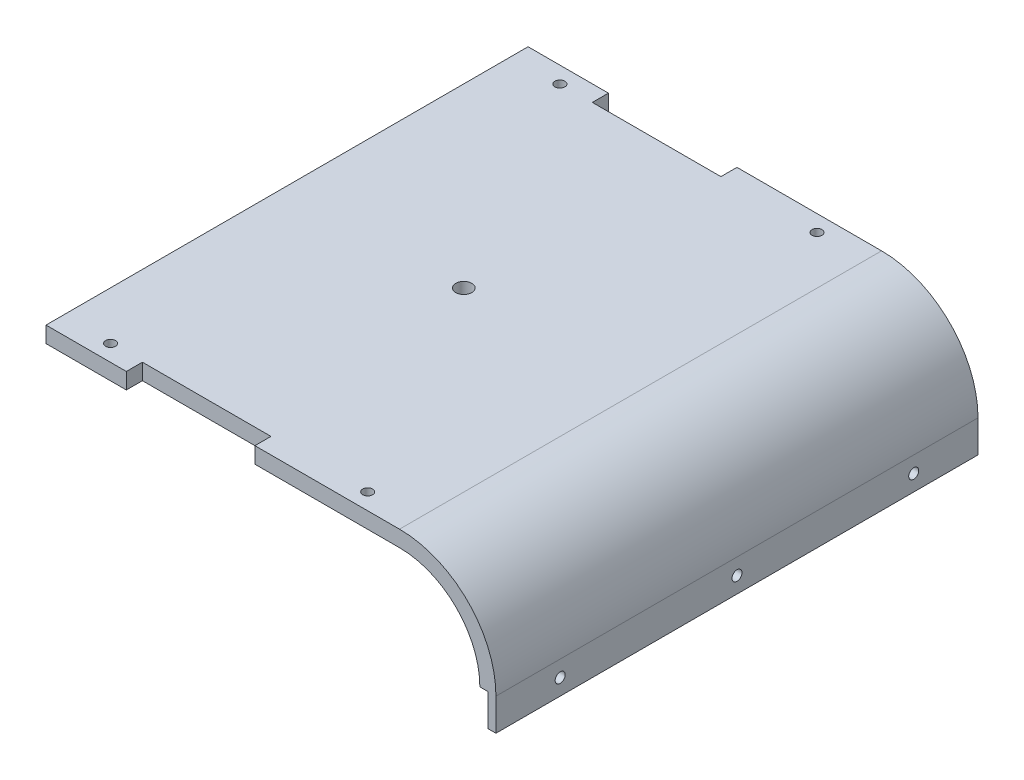
SolidWorks part; units mm, degrees
ref_plane "Front Plane" through (0, 0, 0) normal (0, 0, 1) x (1, 0, 0)
ref_plane "Top Plane" through (0, 0, 0) normal (0, 1, 0) x (1, 0, 0)
ref_plane "Right Plane" through (0, 0, 0) normal (1, 0, 0) x (0, 0, -1)
sketch "Sketch1" plane through (0, 0, 0) normal (0, 0, 1) x (1, 0, 0)
  line L0 (-139.7, 0) -> (139.7, 0)
  line L1 (139.7, 0) -> (139.7, -152.4) construction
  line L2 (139.7, -76.2) -> (215.9, -76.2) construction
  line L3 (-139.7, -12.7) -> (139.7, -12.7)
  line L4 (-139.7, 0) -> (-139.7, -12.7)
  line L5 (215.9, -76.2) -> (203.2, -76.2)
  circle A0 centre (139.7, -76.2) radius 76.2 construction
  arc A1 (139.7, 0) -> (215.9, -76.2) centre (139.7, -76.2) cw
  arc A2 (139.7, -12.7) -> (203.2, -76.2) centre (139.7, -76.2) cw
  point P4 (0, 0)
  dimension "D1" = 152.4
  dimension "D2" = 355.6
  dimension "D3" = 12.7
extrude "Boss-Extrude1" add sketch "Sketch1" along normal blind 190.5 and the other way blind 190.5
sketch "Sketch2" plane through (0, -76.2, 0) normal (0, -1, 0) x (1, 0, 0)
  line L0 (203.2, 190.5) -> (215.9, 190.5) construction
  line L1 (209.55, 190.5) -> (215.9, 190.5)
  line L2 (209.55, 190.5) -> (209.55, -190.5)
  line L3 (209.55, -190.5) -> (215.9, -190.5)
  line L4 (215.9, 190.5) -> (215.9, -190.5)
extrude "Boss-Extrude2" add sketch "Sketch2" along normal blind 25.4
sketch "Sketch3" plane through (215.9, 0, 0) normal (1, 0, 0) x (0, 0, -1)
  line L0 (-190.5, -88.9) -> (190.5, -88.9) construction
  line L1 (-190.5, -101.6) -> (-190.5, -76.2) construction
  line L2 (190.5, -101.6) -> (190.5, -76.2) construction
  line L3 (0, -76.2) -> (0, -101.6) construction
  line L4 (190.5, -76.2) -> (-190.5, -76.2) construction
  line L5 (190.5, -101.6) -> (-190.5, -101.6) construction
  line L6 (139.7, -76.2) -> (139.7, -101.6) construction
  line L7 (-139.7, -76.2) -> (-139.7, -101.6) construction
  circle A0 centre (-139.7, -88.9) radius 3.9687
  circle A1 centre (0, -88.9) radius 3.9687
  circle A2 centre (139.7, -88.9) radius 3.9687
  dimension "D3" = 7.9375
  dimension "D1" = 139.7
  dimension "D2" = 139.7
extrude "Cut-Extrude1" cut sketch "Sketch3" against normal blind 25.4
sketch "Sketch4" plane through (0, 0, 0) normal (0, 1, 0) x (1, 0, 0)
  circle A0 centre (0, 0) radius 6.35
  dimension "D1" = 12.7
extrude "Cut-Extrude2" cut sketch "Sketch4" against normal blind 17.78
sketch "Sketch5" plane through (0, 0, 0) normal (0, 1, 0) x (1, 0, 0)
  line L0 (139.7, 0) -> (101.6, 0) construction
  line L1 (139.7, 190.5) -> (139.7, -190.5) construction
  line L2 (-139.7, 190.5) -> (-139.7, -190.5) construction
  line L3 (0, 177.546) -> (0, -177.546) construction
  line L4 (101.6, 177.546) -> (101.6, -177.546) construction
  line L5 (-101.6, -177.546) -> (-101.6, 177.546) construction
  line L6 (139.7, -190.5) -> (-139.7, -190.5) construction
  line L7 (-101.6, 0) -> (-139.7, 0) construction
  line L8 (-101.6, 0) -> (0, 0) construction
  line L9 (0, 0) -> (101.6, 0) construction
  line L10 (0, -190.5) -> (-76.2, -190.5)
  line L11 (-76.2, -190.5) -> (-76.2, -177.8)
  line L12 (-101.6, 0) -> (0, -177.546) construction
  line L13 (0, 0) -> (-101.6, -177.546) construction
  line L14 (-50.8, -88.773) -> (-50.8, -190.5) construction
  line L15 (-50.8, -190.5) -> (-101.6, -177.546) construction
  line L16 (-76.2, -184.023) -> (-76.2, -133.1595) construction
  line L17 (-76.2, -177.8) -> (0, -177.8)
  line L18 (0, -177.8) -> (25.4, -177.8)
  line L19 (25.4, -177.8) -> (25.4, -190.5)
  line L20 (25.4, -190.5) -> (0, -190.5)
  line L21 (25.4, 177.8) -> (25.4, 190.5)
  line L22 (0, 177.8) -> (25.4, 177.8)
  line L23 (-76.2, 177.8) -> (0, 177.8)
  line L24 (-76.2, 190.5) -> (-76.2, 177.8)
  line L25 (0, 190.5) -> (-76.2, 190.5)
  line L26 (25.4, 190.5) -> (0, 190.5)
  circle A0 centre (-101.6, -177.546) radius 3.937
  circle A1 centre (101.6, -177.546) radius 3.937
  circle A2 centre (101.6, 177.546) radius 3.937
  circle A3 centre (-101.6, 177.546) radius 3.937
  point P11 (0, 0)
  point P15 (101.6, 0)
  point P18 (-101.6, 0)
  dimension "D3" = 7.874
  dimension "D1" = 12.954
  dimension "D2" = 203.2
  dimension "D4" = 101.6
  dimension "D5" = 12.7
extrude "Cut-Extrude3" cut sketch "Sketch5" against normal through all
